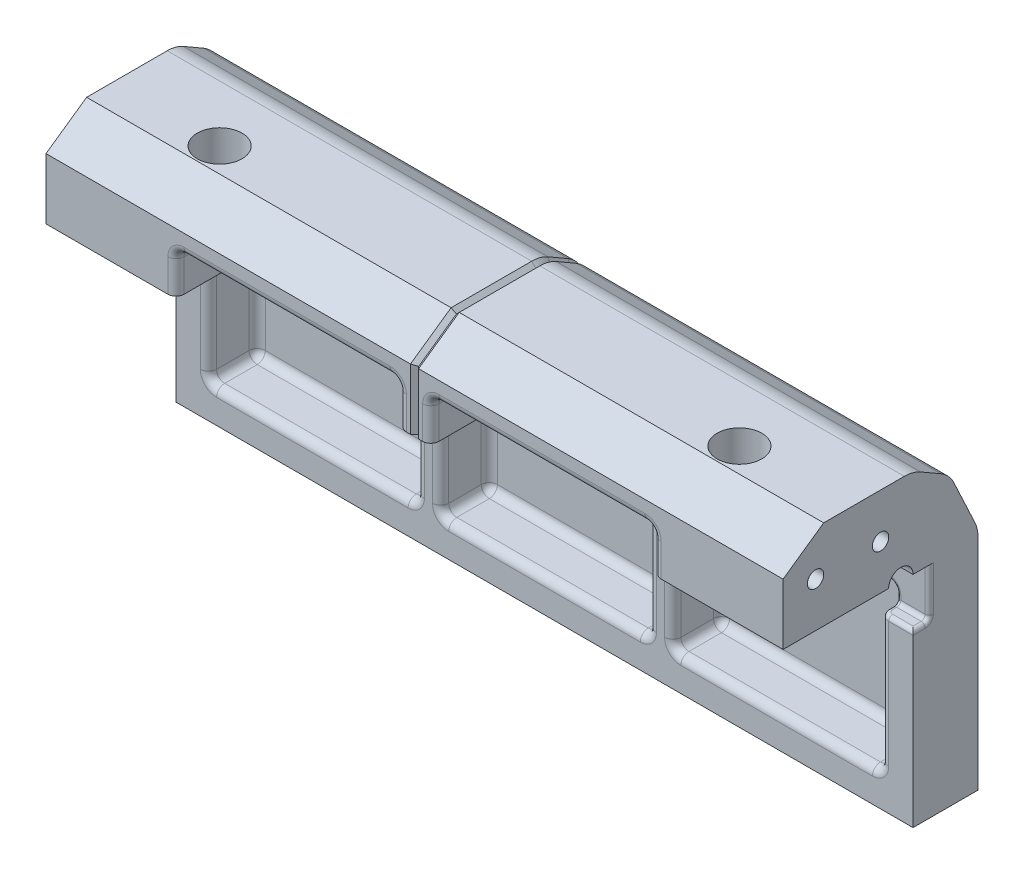
SolidWorks part; units mm, degrees
material "Delrin (Acetal)"
ref_plane "Front Plane" through (0, 0, 0) normal (0, 0, 1) x (1, 0, 0)
ref_plane "Top Plane" through (0, 0, 0) normal (0, 1, 0) x (1, 0, 0)
ref_plane "Right Plane" through (0, 0, 0) normal (1, 0, 0) x (0, 0, -1)
sketch "Sketch1" plane through (0, 0, 0) normal (0, 0, 1) x (1, 0, 0)
  line L1 (-144.0656, 60.325) -> (144.0656, 60.325)
  line L2 (-144.0656, 60.325) -> (-144.0656, -60.325)
  line L3 (-144.0656, -60.325) -> (144.0656, -60.325)
  line L4 (144.0656, 60.325) -> (144.0656, -60.325)
  line L5 (-144.0656, 60.325) -> (144.0656, -60.325) construction
  line L6 (-144.0656, -60.325) -> (144.0656, 60.325) construction
  point P0 (0, 0)
  dimension "FPT" = 288.1313
  dimension "Height" = 120.65
extrude "Extrude1" add sketch "Sketch1" along normal mid plane 76.2
chamfer "Chamfer1" distance 22.225 angle 30 1 edges at (0, 60.325, -38.1) first distance on face at (0, 60.325, 0)
chamfer "Chamfer2" distance 12.7 angle 30 1 edges at (0, 47.4934, -38.1) first distance on face at (0, 53.9092, -26.9875)
sketch "Sketch2" plane through (144.0656, 0, 0) normal (1, 0, 0) x (0, 0, -1)
  line L0 (12.7, 60.325) -> (38.1, 60.325)
  line L1 (-38.1, 60.325) -> (15.875, 60.325) construction
  line L2 (38.1, 60.325) -> (38.1, 45.6603)
  line L3 (38.1, 45.6603) -> (12.7, 60.325)
  line L4 (38.1, -60.325) -> (38.1, 34.7934) construction
  line L5 (-38.1, -60.325) -> (-38.1, 60.325) construction
  dimension "D1" = 30
  dimension "D2" = 50.8
extrude "Cut-Extrude1" cut sketch "Sketch2" against normal up to next
sketch "Sketch3" plane through (144.0656, 0, 0) normal (1, 0, 0) x (0, 0, -1)
  line L0 (26.9875, 52.0761) -> (38.1, 52.0761)
  line L1 (38.1, 52.0761) -> (38.1, 28.2453)
  line L2 (38.1, -60.325) -> (38.1, 34.7934) construction
  line L3 (38.1, 28.2453) -> (26.9875, 52.0761)
  line L4 (12.7, 60.325) -> (28.689, 51.0938) construction
  dimension "D1" = 11.1125
  dimension "D2" = 25
extrude "Cut-Extrude2" cut sketch "Sketch3" against normal up to next
fillet "Fillet1" radius 12.7 3 edges at (0, 28.2453, -38.1) (0, 52.0761, -26.9875) (0, 60.325, -12.7)
hole_wizard "M6 Clearance Hole1" positions "Sketch4" profile "Sketch5" hole size "M6" standard "ANSI Metric"
sketch "Sketch4" plane through (144.0656, 0, 0) normal (1, 0, 0) x (0, 0, -1)
  line L0 (-38.1, 60.325) -> (9.297, 60.325) construction
  line L1 (-25.4, 42.8625) -> (0, 42.8625) construction
  line L2 (-38.1, -60.325) -> (-38.1, 60.325) construction
  point P0 (-25.4, 42.8625)
  point P2 (0, 42.8625)
  dimension "D1" = 25.4
  dimension "D2" = 17.4625
  dimension "D3" = 12.7
sketch "Sketch5" plane through (144.0656, 42.8625, 25.4) normal (0, 1, 0) x (0, 0, -1)
  line L0 (0, 0) -> (0, 27.3228)
  line L1 (0, 27.3228) -> (3.2, 25.4)
  line L2 (3.2, 25.4) -> (3.2, 0)
  line L5 (3.2, 0) -> (0, 0)
  line L10 (0, 27.3228) -> (-3.2, 25.4) construction
  line L11 (0, -6.35) -> (0, 107.95) construction
  dimension "Hole Dia." = 6.4
  dimension "Hole Depth" = 25.4
  dimension "Drill Angle" = 118
chamfer "Chamfer3" distance 15.875 angle 35 1 edges at (0, 60.325, 38.1) first distance on face at (0, 60.325, 14.4015)
sketch "Sketch6" plane through (144.0656, 0, 0) normal (1, 0, 0) x (0, 0, -1)
  line L0 (-38.1, -60.325) -> (-38.1, 49.2092) construction
  line L1 (-38.1, 25.4) -> (12.7, 25.4)
  line L2 (-38.1, 25.4) -> (-38.1, -60.325)
  line L3 (-38.1, -60.325) -> (12.7, -60.325)
  line L4 (12.7, 25.4) -> (12.7, -60.325)
  line L5 (-38.1, -60.325) -> (38.1, -60.325) construction
  line L6 (-22.225, 60.325) -> (9.297, 60.325) construction
  line L7 (38.1, -60.325) -> (38.1, 25.4298) construction
  dimension "D1" = 34.925
  dimension "D2" = 25.4
extrude "Cut-Extrude3" cut sketch "Sketch6" against normal up to next
hole_wizard "CBORE for M6 SHCS1" positions "Sketch9" profile "Sketch10" counterbore size "M6" standard "ANSI Metric" end condition up to next
sketch "Sketch9" plane through (0, 60.325, 0) normal (0, 1, 0) x (1, 0, 0)
  line L0 (-101.6, -12.7) -> (101.6, -12.7) construction
  line L1 (144.0656, -38.1) -> (-144.0656, -38.1) construction
  line L2 (-144.0656, -22.225) -> (-144.0656, 9.297) construction
  point P0 (-101.6, -12.7)
  point P2 (101.6, -12.7)
  point P11 (0, -12.7)
  dimension "D2" = 25.4
  dimension "D3" = 42.4656
sketch "Sketch10" plane through (-101.6, 60.325, 12.7) normal (1, 0, 0) x (0, 0, 1)
  line L0 (0, 0) -> (0, 34.925)
  line L1 (0, 34.925) -> (3.3, 34.925)
  line L3 (3.3, 34.925) -> (3.3, 12.7)
  line L4 (3.3, 12.7) -> (8.7312, 12.7)
  line L5 (8.7312, 12.7) -> (8.7312, 0)
  line L7 (8.7312, 0) -> (0, 0)
  line L11 (0, -6.35) -> (0, 107.95) construction
  dimension "Thru Hole Dia." = 6.6
  dimension "Thru Hole Depth" = 34.925
  dimension "C'Bore Dia." = 17.4625
  dimension "C'Bore Depth" = 12.7
sketch "Sketch11" plane through (144.0656, 0, 0) normal (1, 0, 0) x (0, 0, -1)
  line L0 (12.7, 25.4) -> (-38.1, 25.4) construction
  line L1 (12.7, -60.325) -> (12.7, 25.4) construction
  circle A0 centre (7.9375, 25.4) radius 4.7625
  dimension "D1" = 9.525
extrude "Cut-Extrude5" cut sketch "Sketch11" against normal through all both and the other way through all
sketch "Sketch12" plane through (0, 0, -12.7) normal (0, 0, 1) x (1, 0, 0)
  line L0 (-144.0656, 25.4) -> (-144.0656, -60.325) construction
  line L1 (-131.3656, 12.7) -> (-50.1385, 12.7)
  line L2 (-131.3656, 12.7) -> (-131.3656, -47.625)
  line L3 (-131.3656, -47.625) -> (-50.1385, -47.625)
  line L4 (-50.1385, 12.7) -> (-50.1385, -47.625)
  line L5 (-40.6135, 12.7) -> (40.6135, 12.7)
  line L6 (-40.6135, 12.7) -> (-40.6135, -47.625)
  line L7 (-40.6135, -47.625) -> (40.6135, -47.625)
  line L8 (40.6135, 12.7) -> (40.6135, -47.625)
  line L9 (50.1385, 12.7) -> (131.3656, 12.7)
  line L10 (50.1385, 12.7) -> (50.1385, -47.625)
  line L11 (50.1385, -47.625) -> (131.3656, -47.625)
  line L12 (131.3656, 12.7) -> (131.3656, -47.625)
  line L13 (-144.0656, 25.4) -> (144.0656, 25.4) construction
  line L14 (-144.0656, -60.325) -> (144.0656, -60.325) construction
  point P12 (0, 12.7)
  dimension "D1" = 9.525
  dimension "D2" = 9.525
  dimension "D3" = 12.7
  dimension "D4" = 12.7
  dimension "D5" = 12.7
extrude "Cut-Extrude6" cut sketch "Sketch12" against normal blind 19.05
fillet "Fillet2" radius 3.175 36 edges at (-50.1385, -17.4625, -12.7) (-131.3656, -17.4625, -12.7) (-40.6135, -17.4625, -12.7) (40.6135, -17.4625, -12.7) (131.3656, -17.4625, -12.7) (50.1385, -17.4625, -12.7) (-131.3656, -47.625, -22.225) (-50.1385, -47.625, -22.225) (-90.7521, -47.625, -12.7) (-50.1385, 12.7, -22.225) (-131.3656, 12.7, -22.225) (-90.7521, 12.7, -12.7) (40.6135, 12.7, -22.225) (-40.6135, 12.7, -22.225) (0, 12.7, -12.7) (-40.6135, -47.625, -22.225) (40.6135, -47.625, -22.225) (0, -47.625, -12.7) (50.1385, -47.625, -22.225) (131.3656, -47.625, -22.225) (90.7521, -47.625, -12.7) (131.3656, 12.7, -22.225) (50.1385, 12.7, -22.225) (90.7521, 12.7, -12.7) (90.7521, 12.7, -31.75) (131.3656, -17.4625, -31.75) (90.7521, -47.625, -31.75) (50.1385, -17.4625, -31.75) (0, 12.7, -31.75) (40.6135, -17.4625, -31.75) (0, -47.625, -31.75) (-40.6135, -17.4625, -31.75) (-90.7521, 12.7, -31.75) (-50.1385, -17.4625, -31.75) (-90.7521, -47.625, -31.75) (-131.3656, -17.4625, -31.75)
sketch "Sketch13" plane through (0, 0, 38.1) normal (0, 0, 1) x (1, 0, 0)
  line L0 (-144.0656, 25.4) -> (144.0656, 25.4) construction
  line L1 (-93.2656, 41.275) -> (-6.35, 41.275)
  line L2 (-93.2656, 41.275) -> (-93.2656, 25.4)
  line L3 (-93.2656, 25.4) -> (-6.35, 25.4)
  line L4 (-6.35, 41.275) -> (-6.35, 25.4)
  line L5 (-144.0656, 25.4) -> (144.0656, 25.4) construction
  line L6 (6.35, 41.275) -> (93.2656, 41.275)
  line L7 (6.35, 41.275) -> (6.35, 25.4)
  line L8 (6.35, 25.4) -> (93.2656, 25.4)
  line L9 (93.2656, 41.275) -> (93.2656, 25.4)
  line L10 (-6.35, 41.275) -> (6.35, 41.275) construction
  line L11 (-144.0656, 49.2092) -> (-144.0656, 25.4) construction
  line L12 (-144.0656, 60.325) -> (144.0656, 60.325) construction
  point P12 (0, 41.275)
  dimension "D1" = 12.7
  dimension "D2" = 50.8
  dimension "D3" = 19.05
extrude "Cut-Extrude7" cut sketch "Sketch13" against normal up to surface (50.8 mm away) up to face at (0, -17.4625, -12.7)
fillet "Fillet3" radius 3.175 16 edges at (6.35, 33.3375, 38.1) (93.2656, 33.3375, 38.1) (-93.2656, 33.3375, 38.1) (-6.35, 33.3375, 38.1) (49.8078, 41.275, -12.7) (6.35, 41.275, 12.7) (49.8078, 41.275, 38.1) (93.2656, 41.275, 12.7) (-49.8078, 41.275, -12.7) (-93.2656, 41.275, 12.7) (-49.8078, 41.275, 38.1) (-6.35, 41.275, 12.7) (93.2656, 33.3375, -12.7) (-6.35, 33.3375, -12.7) (6.35, 33.3375, -12.7) (-93.2656, 33.3375, -12.7)
sketch "Sketch16" plane through (0, 0, 0) normal (1, 0, 0) x (0, 0, -1)
  line L10 (12.7, 25.4) -> (12.7, -60.325)
  line L11 (-38.1, 25.4) -> (3.175, 25.4)
  line L12 (-38.1, 49.2092) -> (-38.1, 25.4)
  line L13 (-22.225, 60.325) -> (-38.1, 49.2092)
  line L14 (9.297, 60.325) -> (-22.225, 60.325)
  line L15 (23.5197, 54.0783) -> (15.647, 58.6235)
  line L16 (36.9101, 30.797) -> (28.6798, 48.447)
  line L17 (38.1, -60.325) -> (38.1, 25.4298)
  line L18 (12.7, -60.325) -> (38.1, -60.325)
  line L21 (-38.1, 49.2092) -> (-38.1, 25.4)
  line L22 (-22.225, 60.325) -> (-38.1, 49.2092)
  line L23 (9.297, 60.325) -> (-22.225, 60.325)
  line L24 (23.5197, 54.0783) -> (15.647, 58.6235)
  line L25 (36.9101, 30.797) -> (28.6798, 48.447)
  line L26 (38.1, -60.325) -> (38.1, 25.4298)
  arc A4 (12.7, 25.4) -> (3.175, 25.4) centre (7.9375, 25.4) ccw
  arc A5 (15.647, 58.6235) -> (9.297, 60.325) centre (9.297, 47.625) ccw
  arc A6 (28.6798, 48.447) -> (23.5197, 54.0783) centre (17.1697, 43.0797) ccw
  arc A7 (38.1, 25.4298) -> (36.9101, 30.797) centre (25.4, 25.4298) ccw
  arc A9 (15.647, 58.6235) -> (9.297, 60.325) centre (9.297, 47.625) ccw
  arc A10 (28.6798, 48.447) -> (23.5197, 54.0783) centre (17.1697, 43.0797) ccw
  arc A11 (38.1, 25.4298) -> (36.9101, 30.797) centre (25.4, 25.4298) ccw
  dimension "D1" = 0
sketch "Sketch17" plane through (0, -60.325, 34.925) normal (0, 1, 0) x (-1, 0, 0)
  line L4 (1.5875, -73.025) -> (-1.5875, -73.025)
  line L5 (144.0656, -73.025) -> (-144.0656, -73.025) construction
  line L6 (-1.5875, -73.025) -> (0, -71.4375)
  line L7 (0, -71.4375) -> (1.5875, -73.025)
  line L8 (0, -12.7) -> (0, 3.175) construction
  line L9 (0, -44.222) -> (0, -12.7) construction
  point P9 (0, -73.025)
  dimension "D1" = 3.175
  dimension "D2" = 1.5875
sweep "Cut-Sweep2" cut profiles "Sketch17" path "Sketch16"
sketch "Sketch20" plane through (0, 25.4, 0) normal (0, -1, 0) x (1, 0, 0)
  line L0 (121.7136, 12.7) -> (128.3176, 12.7) construction
  line L1 (121.7136, 33.7344) -> (128.3176, 33.7344)
  line L2 (121.7136, 33.7344) -> (121.7136, -8.3344)
  line L3 (121.7136, -8.3344) -> (128.3176, -8.3344)
  line L4 (128.3176, 33.7344) -> (128.3176, -8.3344)
  line L5 (96.4406, 38.1) -> (144.0656, 38.1) construction
  line L6 (125.0156, 33.7344) -> (125.0156, -8.3344) construction
  line L7 (144.0656, -3.175) -> (144.0656, 38.1) construction
  dimension "D1" = 25.4
  dimension "D2" = 42.0688
  dimension "D3" = 19.05
  dimension "D4" = 6.604
extrude "Cut-Extrude10" cut sketch "Sketch20" against normal blind 25.4
fillet "Fillet4" radius 0.7937 14 edges at (128.3176, 28.9051, -4.7133) (121.7136, 28.9051, -4.7133) (128.3176, 25.4, 15.2797) (121.7136, 25.4, 15.2797) (125.0156, 30.1459, -8.3344) (121.7136, 40.473, -8.3344) (125.0156, 50.8, -8.3344) (128.3176, 40.473, -8.3344) (128.3176, 38.1, 33.7344) (125.0156, 50.8, 33.7344) (121.7136, 38.1, 33.7344) (125.0156, 25.4, 33.7344) (128.3176, 50.8, 12.7) (121.7136, 50.8, 12.7)
mirror "Mirror1" about plane through (0, 0, 0) normal (1, 0, 0) of "Cut-Extrude10", "Fillet4", "M6 Clearance Hole1"
sketch "Sketch21" plane through (0, 0, -12.7) normal (0, 0, 1) x (1, 0, 0)
  line L0 (144.0656, -60.325) -> (144.0656, 25.4) construction
  line L1 (-144.0656, 25.4) -> (144.0656, 25.4)
  line L2 (-144.0656, 25.4) -> (-144.0656, 6.35)
  line L3 (-144.0656, 6.35) -> (144.0656, 6.35)
  line L4 (144.0656, 25.4) -> (144.0656, 6.35)
  dimension "D1" = 19.05
extrude "Cut-Extrude11" cut sketch "Sketch21" against normal blind 6.35
fillet "Fillet5" radius 1.5875 39 edges at (-40.6135, 7.9375, -19.05) (-40.6135, 6.35, -17.4625) (-39.6836, 11.7701, -19.05) (-41.5435, 6.35, -13.6299) (0, 12.7, -19.05) (-45.376, 6.35, -12.7) (39.6836, 11.7701, -19.05) (-49.2086, 6.35, -13.6299) (40.6135, 7.9375, -19.05) (-50.1385, 6.35, -17.4625) (40.6135, 6.35, -17.4625) (-50.1385, 7.9375, -19.05) (41.5435, 6.35, -13.6299) (-51.0685, 11.7701, -19.05) (45.376, 6.35, -12.7) (-90.7521, 12.7, -19.05) (49.2086, 6.35, -13.6299) (132.2956, 6.35, -13.6299) (-130.4357, 11.7701, -19.05) (50.1385, 6.35, -17.4625) (131.3656, 6.35, -17.4625) (-131.3656, 7.9375, -19.05) (-144.0656, 6.35, -15.875) (50.1385, 7.9375, -19.05) (51.0685, 11.7701, -19.05) (131.3656, 7.9375, -19.05) (130.4357, 11.7701, -19.05) (-131.3656, 6.35, -17.4625) (-132.2956, 6.35, -13.6299) (-144.0656, 15.875, -19.05) (144.0656, 15.875, -19.05) (137.7156, 6.35, -19.05) (45.376, 6.35, -19.05) (90.7521, 12.7, -19.05) (-45.376, 6.35, -19.05) (-139.3031, 6.35, -12.7) (-137.7156, 6.35, -19.05)
